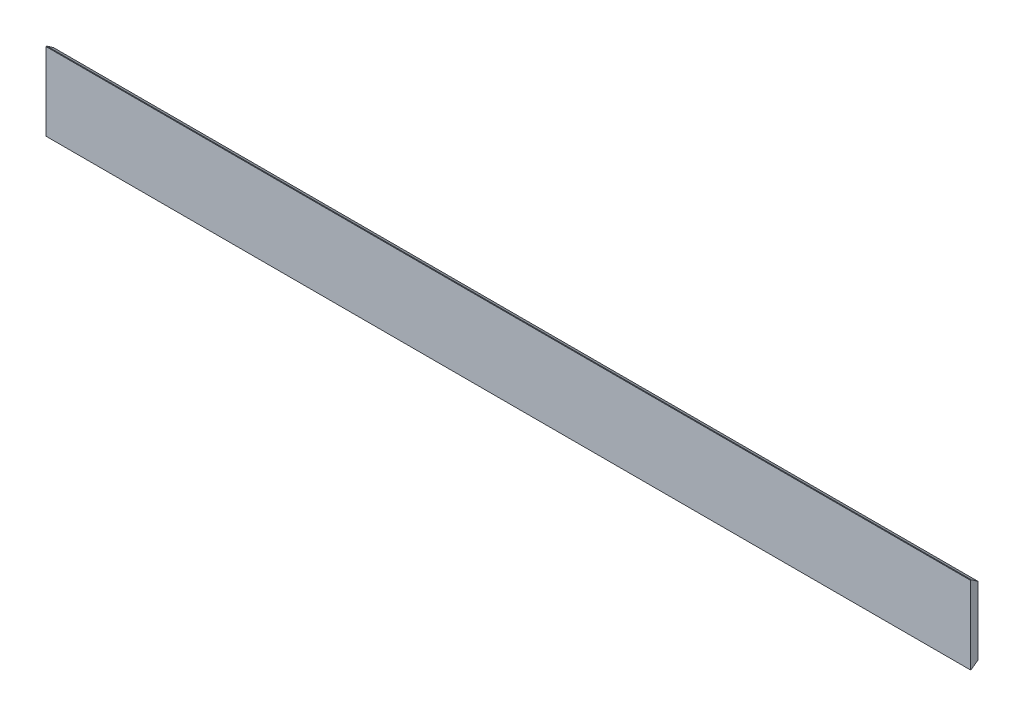
SolidWorks part; units mm, degrees
note: The reader was unsure of these and kept them because the rebuilt part matched: thickness of "基体-法兰1", "钣金6", "钣金7".
ref_plane "前视基准面" through (0, 0, 0) normal (0, 0, 1) x (1, 0, 0)
ref_plane "上视基准面" through (0, 0, 0) normal (0, 1, 0) x (1, 0, 0)
ref_plane "右视基准面" through (0, 0, 0) normal (1, 0, 0) x (0, 0, -1)
sketch "草图1" plane through (0, 0, 0) normal (0, 0, 1) x (1, 0, 0)
  line L1 (-1095, 92) -> (1095, 92)
  line L2 (-1095, 92) -> (-1095, -92)
  line L3 (-1095, -92) -> (1095, -92)
  line L4 (1095, 92) -> (1095, -92)
  line L5 (-1095, 92) -> (1095, -92) construction
  line L6 (-1095, -92) -> (1095, 92) construction
  point P0 (0, 0)
  dimension "D1" = 2190
  dimension "D2" = 184
base flange "基体-法兰1" sketch "草图1" thickness 18 reverse thickness direction no parameters "D1"=1
sketch "草图6" plane through (-1095, 0, 0) normal (-1, 0, 0) x (0, 0, 1)
  line L0 (-18, 92) -> (-18, 80.7967)
  line L1 (-18, 92) -> (-18, -92) construction
  line L2 (-18, 80.7967) -> (-2, 92)
  line L3 (-18, 92) -> (0, 92) construction
  line L4 (-2, 92) -> (-18, 92)
  line L5 (-18, -92) -> (-18, -80.7967)
  line L6 (-18, -80.7967) -> (-2, -92)
  line L7 (-18, -92) -> (0, -92) construction
  line L8 (-2, -92) -> (-18, -92)
  dimension "D1" = 16
  dimension "D2" = 16
  dimension "D3" = 35
  dimension "D4" = 35
extrude "切除-拉伸1" cut sketch "草图6" against normal through all normal cut yes
sketch "折弯-线1" plane through (0, 0, 0) normal (0, 1, 0) x (1, 0, 0)
sketch "边界框1" plane through (0, 0, 0) normal (0, 1, 0) x (1, 0, 0)
sheet metal parameters "钣金6" thickness 18 parameters "D1"=1, "D7"=20
flat pattern "平板型式6" [suppressed]
sketch "折弯-线2" plane through (0, 0, 0) normal (0, 1, 0) x (1, 0, 0)
sketch "边界框2" [suppressed] plane through (0, 0, 0) normal (0, 1, 0) x (1, 0, 0)
sheet metal parameters "钣金7" thickness 18 parameters "D1"=1, "D7"=20
flat pattern "平板型式6"
sketch "折弯-线2" plane through (0, 0, 0) normal (0, 1, 0) x (1, 0, 0)
sketch "边界框2" [suppressed] plane through (0, 0, 0) normal (0, 1, 0) x (1, 0, 0)
